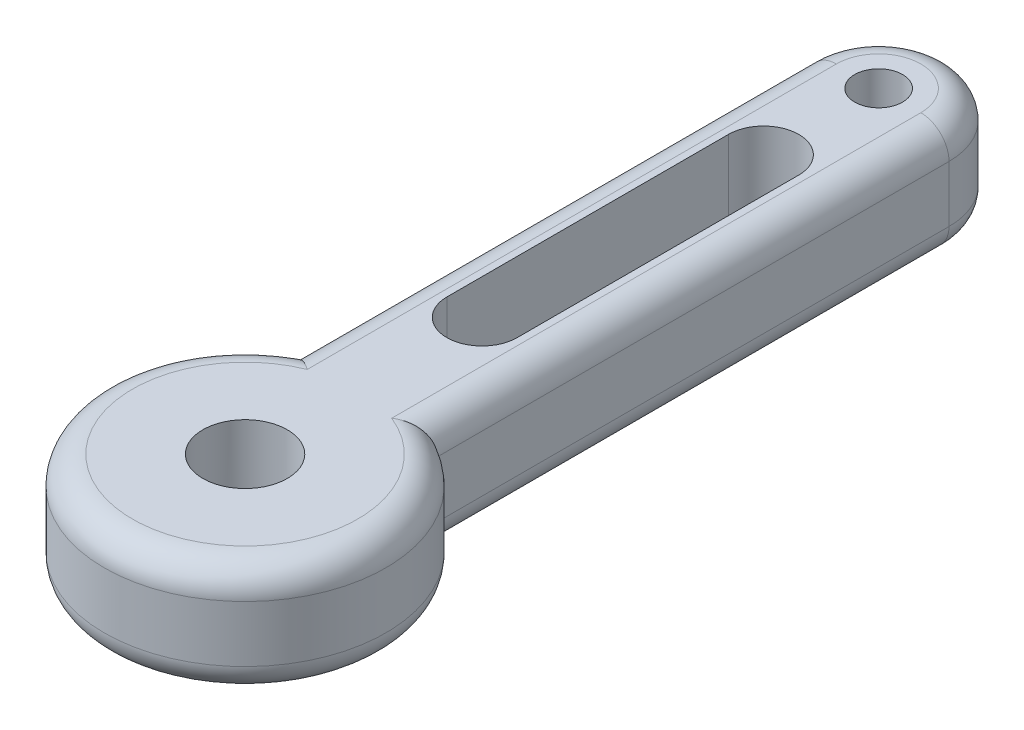
SolidWorks part; units mm, degrees
ref_plane "前视基准面" through (0, 0, 0) normal (0, 0, 1) x (1, 0, 0)
ref_plane "上视基准面" through (0, 0, 0) normal (0, 1, 0) x (1, 0, 0)
ref_plane "右视基准面" through (0, 0, 0) normal (1, 0, 0) x (0, 0, -1)
other "Configuration Table"
sketch "草图1" plane through (0, 0, 0) normal (0, 1, 0) x (1, 0, 0)
  line L0 (0, 0) -> (0, 45)
  line L1 (-5, 45) -> (-5, 8.6603)
  line L2 (5, 45) -> (5, 8.6603)
  circle A0 centre (0, 0) radius 10
  circle A1 centre (0, 45) radius 5
  dimension "D1" = 20
extrude "凸台-拉伸1" add sketch "草图1" along normal blind 8 contours A0 | A1 L0 A0 L2 | A1 L1 A0 L0 | A1 region at (-2.5646, 0, -25.3368) region at (2.5646, 0, -25.3368) region at (2.515, 0, -9.3861) region at (-3.4355, 0, -41.5645)
sketch "草图2" plane through (0, 8, 0) normal (0, 1, 0) x (1, 0, 0)
  line L0 (5, 45) -> (5, 8.6603) construction
  line L1 (-5, 45) -> (-5, 8.6603) construction
  line L2 (5, 8.6603) -> (5, 45)
  line L3 (-5, 45) -> (-5, 8.6603)
  line L4 (5, 8.6603) -> (5, 45)
  line L5 (-5, 45) -> (-5, 8.6603)
  line L6 (0, 0) -> (0, 45) construction
  line L7 (5, 45) -> (5, 8.6603)
  line L8 (-5, 45) -> (-5, 8.6603)
  line L9 (0, 0) -> (0, 45)
  circle A0 centre (0, 0) radius 3
  circle A1 centre (0, 45) radius 5
  arc A2 (5, 45) -> (-5, 45) centre (0, 45) ccw
  arc A3 (-5, 8.6603) -> (5, 8.6603) centre (0, 0) ccw
  arc A4 (5, 45) -> (-5, 45) centre (0, 45) ccw
  arc A5 (-5, 8.6603) -> (5, 8.6603) centre (0, 0) ccw
  circle A6 centre (0, 45) radius 5
  circle A7 centre (0, 0) radius 10
  circle A8 centre (0, 0) radius 10
  dimension "D1" = 0
  dimension "D2" = 0
  dimension "D3" = 0
extrude "切除-拉伸1" cut sketch "草图2" against normal up to next contours A0 region at (2.0613, 8, -2.0613)
sketch "草图3" plane through (0, 0, 0) normal (0, -1, 0) x (1, 0, 0)
  line L0 (0, 0) -> (0, -10)
  line L1 (-1.99, -10.2) -> (-2.985, -0.3)
  line L2 (5, -45) -> (5, -8.6603)
  line L3 (-5, -8.6603) -> (-5, -45)
  line L4 (5, -45) -> (5, -8.6603)
  line L5 (-5, -8.6603) -> (-5, -45)
  line L6 (2.985, -0.3) -> (1.8987, -10.6283)
  circle A0 centre (0, 0) radius 3
  circle A1 centre (0, -10) radius 2
  arc A2 (5, -8.6603) -> (-5, -8.6603) centre (0, 0) ccw
  arc A3 (-5, -45) -> (5, -45) centre (0, -45) ccw
  arc A4 (5, -8.6603) -> (-5, -8.6603) centre (0, 0) ccw
  arc A5 (-5, -45) -> (5, -45) centre (0, -45) ccw
  circle M7 centre (0, 0) radius 3
  dimension "D1" = 0
extrude "切除-拉伸2" cut sketch "草图3" against normal blind 3 contours A1 L6 L0 M7 | A1 L0 L1 M7 | L6 A1 | L6 M7 region at (0.4611, 0, -1.8165) region at (-1.3622, 0, -5.331) region at (-0.0041, 0, -9.9996)
sketch "草图4" plane through (0, 8, 0) normal (0, 1, 0) x (1, 0, 0)
  line L0 (5, 45) -> (5, 8.6603) construction
  line L1 (-5, 45) -> (-5, 8.6603) construction
  line L2 (5, 8.6603) -> (5, 45)
  line L3 (-5, 45) -> (-5, 8.6603)
  line L4 (5, 8.6603) -> (5, 45)
  line L5 (-5, 45) -> (-5, 8.6603)
  line L6 (0, 0) -> (0, 45) construction
  line L7 (5, 45) -> (5, 8.6603)
  line L8 (-5, 45) -> (-5, 8.6603)
  line L9 (0, 0) -> (0, 45)
  circle A0 centre (0, 45) radius 1.7
  circle A1 centre (0, 45) radius 5
  arc A2 (5, 45) -> (-5, 45) centre (0, 45) ccw
  arc A3 (-5, 8.6603) -> (5, 8.6603) centre (0, 0) ccw
  arc A4 (5, 45) -> (-5, 45) centre (0, 45) ccw
  arc A5 (-5, 8.6603) -> (5, 8.6603) centre (0, 0) ccw
  circle A6 centre (0, 45) radius 5
  circle A7 centre (0, 0) radius 10
  circle A8 centre (0, 0) radius 10
  dimension "D1" = 0
  dimension "D2" = 0
  dimension "D3" = 0
extrude "切除-拉伸3" cut sketch "草图4" against normal up to next contours A0 region at (-1.1681, 8, -46.1681)
sketch "草图5" plane through (0, 0, 0) normal (0, -1, 0) x (1, 0, 0)
  line L0 (-5, -26.8301) -> (0, -26.8301)
  line L1 (0, -36.8301) -> (0, -16.8301) construction
  line L2 (5, -45) -> (5, -8.6603)
  line L3 (-5, -8.6603) -> (-5, -45)
  line L4 (5, -45) -> (5, -8.6603)
  line L5 (-5, -8.6603) -> (-5, -45)
  line L6 (-2.5, -36.8301) -> (-2.5, -16.8301)
  line L7 (2.5, -36.8301) -> (2.5, -16.8301)
  arc A0 (-2.5, -36.8301) -> (2.5, -36.8301) centre (0, -36.8301) ccw
  arc A1 (2.5, -16.8301) -> (-2.5, -16.8301) centre (0, -16.8301) ccw
  arc A2 (5, -8.6603) -> (-5, -8.6603) centre (0, 0) ccw
  arc A3 (-5, -45) -> (5, -45) centre (0, -45) ccw
  arc A4 (5, -8.6603) -> (-5, -8.6603) centre (0, 0) ccw
  arc A5 (-5, -45) -> (5, -45) centre (0, -45) ccw
  point P10 (0, -26.8301)
  dimension "D1" = 0
extrude "切除-拉伸4" cut sketch "草图5" against normal up to next contours L7 A1 L6 A0 region at (-2.245, 0, -21.8301)
fillet "圆角2" radius 2 8 edges at (0, 0, 10) (-5, 0, -26.8301) (0, 0, -50) (5, 0, -26.8301) (0, 8, 10) (5, 8, -26.8301) (0, 8, -50) (-5, 8, -26.8301)
